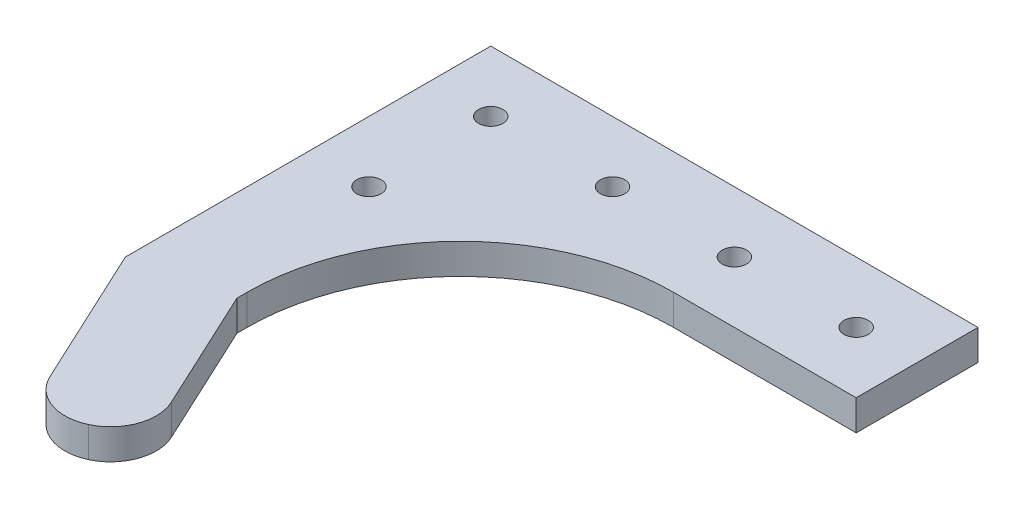
SolidWorks part; units mm, degrees
material "6061-T6 (SS)"
ref_plane "Front Plane" through (0, 0, 0) normal (0, 0, 1) x (1, 0, 0)
ref_plane "Top Plane" through (0, 0, 0) normal (0, 1, 0) x (1, 0, 0)
ref_plane "Right Plane" through (0, 0, 0) normal (1, 0, 0) x (0, 0, -1)
sketch "Sketch1" plane through (0, 0, 0) normal (0, 1, 0) x (1, 0, 0)
  line L0 (0, 0) -> (0, -76.2)
  line L1 (0, 0) -> (101.6, 0)
  line L2 (0, -76.2) -> (17.7663, -114.3)
  line L3 (17.7663, -114.3) -> (35.0315, -106.2491)
  line L4 (35.0315, -106.2491) -> (19.05, -71.9767)
  line L5 (19.05, -71.9767) -> (19.05, -69.85)
  line L6 (63.5, -25.4) -> (101.6, -25.4)
  line L7 (101.6, -25.4) -> (101.6, 0)
  line L8 (63.5, -25.4) -> (0, -25.4) construction
  line L9 (19.05, -69.85) -> (19.05, 0) construction
  line L10 (0, -76.2) -> (0, -215.3196) construction
  line L11 (0, -76.2) -> (19.05, -71.9767) construction
  arc A0 (19.05, -69.85) -> (63.5, -25.4) centre (63.5, -69.85) cw
  dimension "D1" = 44.45
  dimension "D2" = 76.2
  dimension "D3" = 25.4
  dimension "D4" = 19.05
  dimension "D5" = 19.05
  dimension "D6" = 25
  dimension "D7" = 38.1
  dimension "D8" = 101.6
extrude "Boss-Extrude1" add sketch "Sketch1" along normal blind 6.35
sketch "Sketch2" plane through (0, 6.35, 0) normal (0, 1, 0) x (1, 0, 0)
  line L0 (0, -12.7) -> (101.6, -12.7) construction
  line L1 (0, 0) -> (0, -76.2) construction
  line L2 (101.6, -25.4) -> (101.6, 0) construction
  circle A0 centre (12.7, -12.7) radius 2.54
  circle A1 centre (38.1, -12.7) radius 2.54
  circle A2 centre (63.5, -12.7) radius 2.54
  circle A3 centre (88.9, -12.7) radius 2.54
  circle A4 centre (114.3, -12.7) radius 2.54
  circle A5 centre (139.7, -12.7) radius 2.54
  circle A6 centre (12.7, -38.1) radius 2.54
  dimension "D2" = 12.7
  dimension "D8" = 25.4
  dimension "D9" = 5.08
  dimension "D3" = 25.4
  dimension "D4" = 25.4
  dimension "D5" = 25.4
  dimension "D6" = 25.4
  dimension "D7" = 25.4
extrude "Cut-Extrude1" cut sketch "Sketch2" against normal blind 6.35
fillet "Fillet1" radius 9.525 2 edges at (17.7663, 3.175, 114.3) (35.0315, 3.175, 106.2491)
